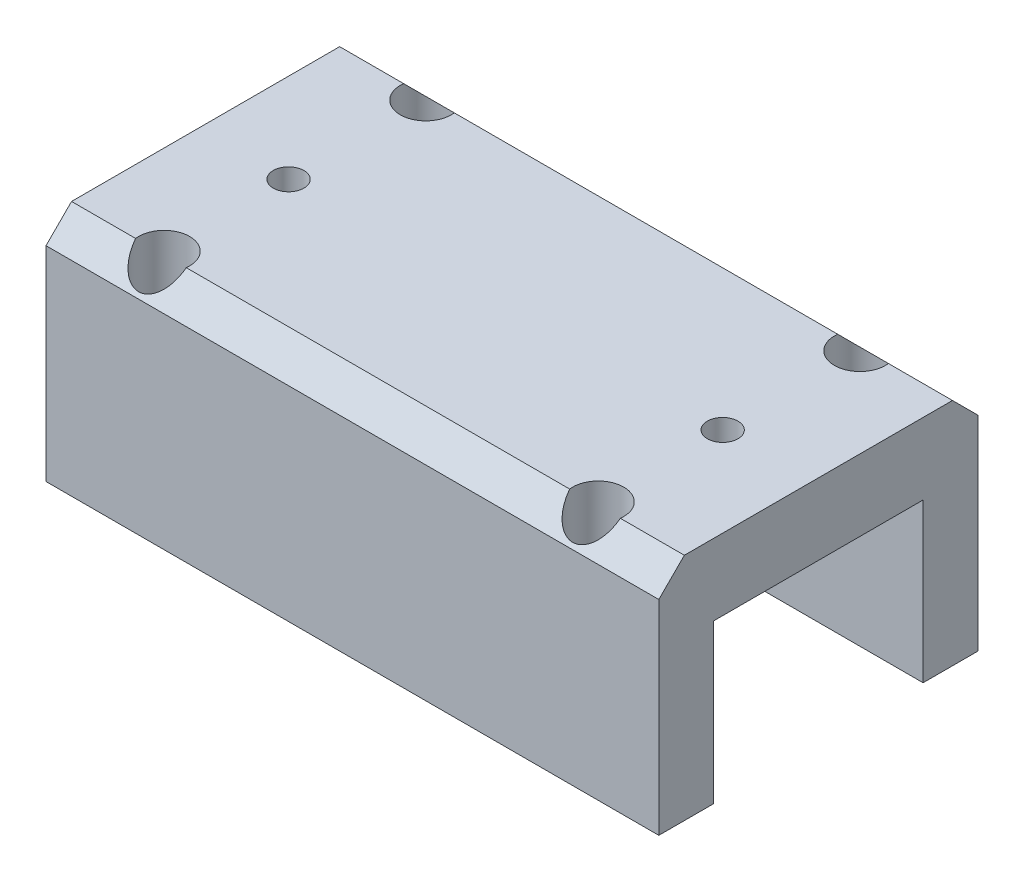
SolidWorks part; units mm, degrees
ref_plane "Front" through (0, 0, 0) normal (0, 0, 1) x (1, 0, 0)
ref_plane "Top" through (0, 0, 0) normal (0, 1, 0) x (1, 0, 0)
ref_plane "Right" through (0, 0, 0) normal (1, 0, 0) x (0, 0, -1)
sketch "草图1" plane through (0, 0, 0) normal (0, 1, 0) x (1, 0, 0)
  line L1 (12, -6.25) -> (-12, -6.25)
  line L2 (12, -6.25) -> (12, 6.25)
  line L3 (12, 6.25) -> (-12, 6.25)
  line L4 (-12, -6.25) -> (-12, 6.25)
  line L5 (12, -6.25) -> (-12, 6.25) construction
  line L6 (12, 6.25) -> (-12, -6.25) construction
  point P0 (0, 0)
  dimension "D1" = 12.5
  dimension "D2" = 24
extrude "凸台-拉伸1" add sketch "草图1" along normal blind 9
sketch "草图2" plane through (0, 0, 0) normal (0, -1, 0) x (1, 0, 0)
  line L5 (-12, -6.25) -> (-12, 6.25) construction
  line L6 (12, -4.1) -> (-12, -4.1)
  line L7 (0, 11.7189) -> (0, -10.1925) construction
  line L10 (12, -4.1) -> (12, 4.1)
  line L11 (12, 4.1) -> (-12, 4.1)
  line L12 (-12, -4.1) -> (-12, 4.1)
  line L13 (12, -4.1) -> (-12, 4.1) construction
  line L14 (12, 4.1) -> (-12, -4.1) construction
  point P0 (0, 0)
  dimension "D1" = 8.2
extrude "切除-拉伸1" cut sketch "草图2" against normal blind 6.2
sketch "草图3" plane through (0, 9, 0) normal (0, 1, 0) x (1, 0, 0)
  line L0 (-8.5, 10.815) -> (-8.5, -9.47) construction
  line L3 (0, 17.304) -> (0, -13.1079) construction
  line L4 (-32.2128, 0) -> (28.324, 0) construction
  circle A0 centre (-8.5, 5.125) radius 0.5
  circle A3 centre (8.5, 5.125) radius 0.5
  circle A4 centre (8.5, -5.125) radius 0.5
  circle A5 centre (-8.5, -5.125) radius 0.5
  dimension "D1" = 1
  dimension "D3" = 10.25
  dimension "D2" = 17
extrude "切除-拉伸2" cut sketch "草图3" against normal through all
sketch "草图4" plane through (0, 9, 0) normal (0, 1, 0) x (1, 0, 0)
  line L0 (0, 15.596) -> (0, -12.9404) construction
  line L1 (-20.1195, -0.25) -> (17.1939, -0.25) construction
  line L3 (-12, -6.25) -> (12, -6.25) construction
  circle A0 centre (-8.5, -0.25) radius 0.6
  circle A1 centre (8.5, -0.25) radius 0.6
  dimension "D1" = 1.2
  dimension "D2" = 17
  dimension "D3" = 6
extrude "切除-拉伸3" cut sketch "草图4" against normal through all
sketch "草图5" plane through (0, 9, 0) normal (0, 1, 0) x (1, 0, 0)
  circle A0 centre (-8.5, 5.125) radius 1
  circle A9 centre (8.5, 5.125) radius 1
  circle A10 centre (8.5, 5.125) radius 0.5 construction
  circle A11 centre (-8.5, -5.125) radius 1
  circle A12 centre (-8.5, -5.125) radius 0.5 construction
  circle A13 centre (8.5, -5.125) radius 1
  circle A14 centre (8.5, -5.125) radius 0.5 construction
  dimension "D1" = 2
extrude "切除-拉伸4" cut sketch "草图5" against normal blind 7
chamfer "倒角1" distance 1 angle 45 2 edges at (0, 9, 6.25) (0, 9, -6.25)
